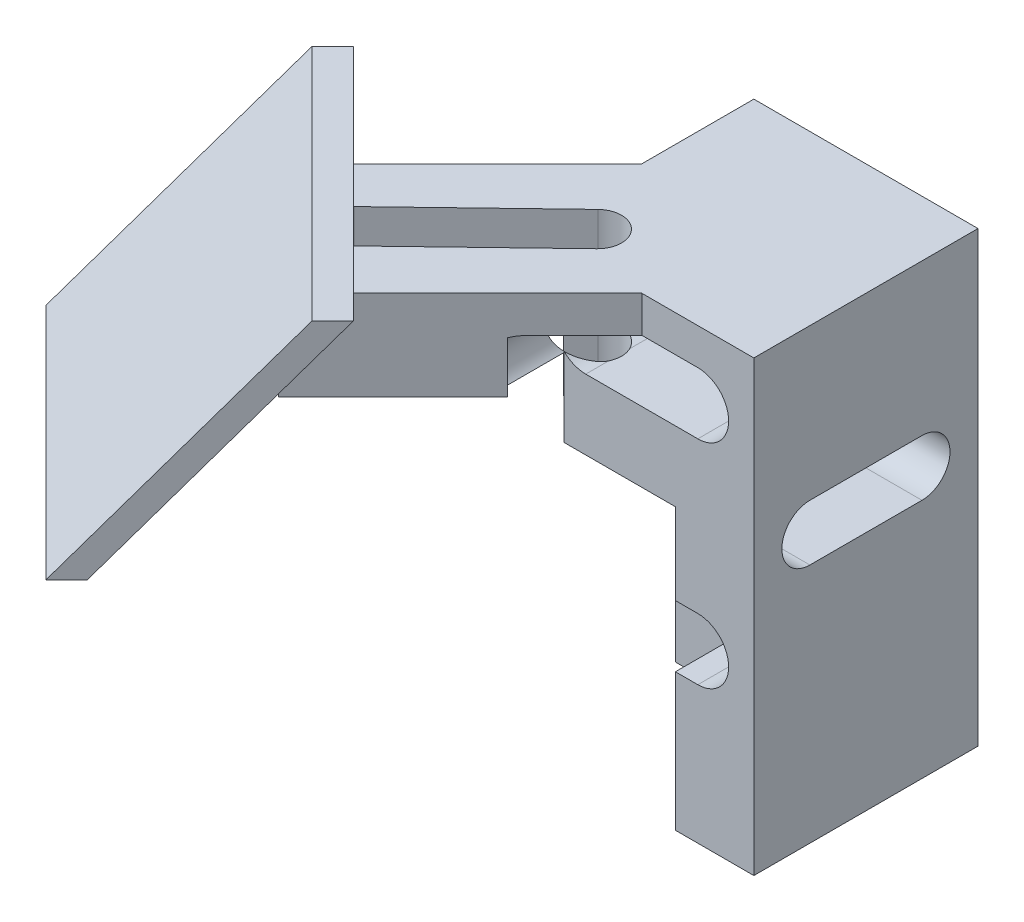
SolidWorks part; units mm, degrees
ref_plane "前视基准面" through (0, 0, 0) normal (0, 0, 1) x (1, 0, 0)
ref_plane "上视基准面" through (0, 0, 0) normal (0, 1, 0) x (1, 0, 0)
ref_plane "右视基准面" through (0, 0, 0) normal (1, 0, 0) x (0, 0, -1)
other "Configuration Table"
sketch "草图1" plane through (0, 0, 0) normal (1, 0, 0) x (0, 0, -1)
  line L1 (-10, -25) -> (10, -25)
  line L2 (-10, -25) -> (-10, 25)
  line L3 (-10, 25) -> (10, 25)
  line L4 (10, -25) -> (10, 25)
  line L5 (-10, -25) -> (10, 25) construction
  line L6 (-10, 25) -> (10, -25) construction
  point P0 (0, 0)
  dimension "D1" = 50
  dimension "D2" = 20
extrude "凸台-拉伸2" add sketch "草图1" along normal blind 20
sketch "草图2" plane through (20, 0, 0) normal (1, 0, 0) x (0, 0, -1)
  line L0 (10, -25) -> (10, 25) construction
  line L1 (-10, -25) -> (10, -25)
  line L2 (-10, -25) -> (-10, -15)
  line L3 (-10, -15) -> (10, -15)
  line L4 (10, -25) -> (10, -15)
  dimension "D1" = 10
extrude "切除-拉伸1" cut sketch "草图2" against normal blind 20
sketch "草图3" plane through (0, 0, -10) normal (0, 0, -1) x (-1, 0, 0)
  line L0 (-15, 19) -> (-5, 19) construction
  line L1 (-15, 21.75) -> (-5, 21.75)
  line L2 (-15, 16.25) -> (-5, 16.25)
  line L3 (0, -15) -> (0, 25) construction
  line L4 (-20, 25) -> (0, 25) construction
  arc A0 (-15, 21.75) -> (-15, 16.25) centre (-15, 19) ccw
  arc A1 (-5, 16.25) -> (-5, 21.75) centre (-5, 19) ccw
  point P2 (-10, 19)
  dimension "D1" = 5.5
  dimension "D2" = 5
  dimension "D3" = 10
  dimension "D4" = 6
extrude "切除-拉伸2" cut sketch "草图3" against normal blind 20
sketch "草图4" plane through (0, 0, 0) normal (-1, 0, 0) x (0, 0, 1)
  line L0 (-5, 9) -> (5, 9) construction
  line L1 (-5, 11.5) -> (5, 11.5)
  line L2 (-5, 6.5) -> (5, 6.5)
  line L3 (-10, -15) -> (10, -15) construction
  line L4 (10, 25) -> (10, -15) construction
  line L5 (-10, -15) -> (-10, 25) construction
  arc A0 (-5, 11.5) -> (-5, 6.5) centre (-5, 9) ccw
  arc A1 (5, 6.5) -> (5, 11.5) centre (5, 9) ccw
  point P2 (0, 9)
  dimension "D1" = 5
  dimension "D2" = 24
  dimension "D3" = 5
  dimension "D4" = 5
extrude "切除-拉伸3" cut sketch "草图4" against normal blind 20
sketch "草图5" plane through (0, 0, -10) normal (0, 0, -1) x (-1, 0, 0)
  line L0 (-15, 0) -> (-5, 0) construction
  line L1 (-15, 2.75) -> (-5, 2.75)
  line L2 (-15, -2.75) -> (-5, -2.75)
  line L3 (0, -15) -> (0, 25) construction
  line L4 (-20, -15) -> (-20, 25) construction
  line L5 (0, -15) -> (-20, -15) construction
  arc A0 (-15, 2.75) -> (-15, -2.75) centre (-15, 0) ccw
  arc A1 (-5, -2.75) -> (-5, 2.75) centre (-5, 0) ccw
  point P2 (-10, 0)
  dimension "D1" = 5
  dimension "D2" = 5
  dimension "D3" = 15
  dimension "D4" = 5.5
extrude "切除-拉伸4" cut sketch "草图5" against normal blind 20
sketch "草图6" plane through (0, -15, 0) normal (0, -1, 0) x (1, 0, 0)
  line L1 (0, 10) -> (13, 10)
  line L2 (0, 10) -> (0, -3)
  line L3 (0, -3) -> (13, -3)
  line L4 (13, 10) -> (13, -3)
  dimension "D1" = 13
  dimension "D2" = 13
extrude "切除-拉伸5" cut sketch "草图6" against normal blind 25
sketch "草图7" plane through (0, 25, 0) normal (0, 1, 0) x (1, 0, 0)
  line L2 (-16.2132, -16.2132) -> (-6.2132, -26.2132)
  line L3 (10, -10) -> (-6.2132, -26.2132)
  line L4 (20, -10) -> (0, -10) construction
  line L5 (0, 0) -> (-16.2132, -16.2132)
  line L6 (0, 10) -> (0, -10) construction
  line L9 (0, 0) -> (10, -10)
extrude "凸台-拉伸3" add sketch "草图7" against normal blind 8
sketch "草图8" plane through (0, 0, 0) normal (-0.7071, 0, -0.7071) x (-0.7071, 0, 0.7071)
  line L0 (18.1973, 27) -> (34.9793, 7)
  line L1 (0, 17) -> (22.9289, 17) construction
  line L3 (18.1973, 27) -> (20.8081, 27)
  line L4 (0, 25) -> (22.9289, 25) construction
  line L5 (20.8081, 27) -> (37.5901, 7)
  line L6 (13.5331, 32.5586) -> (41.8315, -1.1662) construction
  line L7 (15.0652, 33.8441) -> (43.3636, 0.1194) construction
  line L8 (34.9793, 7) -> (37.5901, 7)
  dimension "D1" = 130
  dimension "D3" = 2
  dimension "D5" = 10
  dimension "D4" = 2
extrude "凸台-拉伸6" add sketch "草图8" along normal blind 10 and the other way blind 20
sketch "草图11" plane through (10, 0, 10) normal (0.7071, 0, 0.7071) x (0.7071, 0, -0.7071)
  line L3 (-22.9289, 24.4725) -> (-22.4863, 25)
  line L4 (-22.4863, 25) -> (-22.9289, 25)
  line L5 (-22.9289, 25) -> (-22.9289, 24.4725)
  line L6 (-22.9289, 24.4725) -> (-22.4863, 25)
  line L7 (-22.4863, 25) -> (-22.9289, 25)
  line L8 (-22.9289, 25) -> (-22.9289, 24.4725)
  dimension "D1" = 0
extrude "切除-拉伸7" cut sketch "草图11" against normal blind 18
sketch "草图12" plane through (0, 0, -10) normal (0, 0, -1) x (-1, 0, 0)
  line L0 (-15, 16.25) -> (-5, 16.25) construction
  line L1 (-5, 21.75) -> (-15, 21.75) construction
  line L2 (-15, 16.25) -> (-5, 16.25)
  line L3 (-5, 21.75) -> (-15, 21.75)
  arc A0 (-5, 16.25) -> (-5, 21.75) centre (-5, 19) ccw construction
  arc A1 (-15, 21.75) -> (-15, 16.25) centre (-15, 19) ccw construction
  arc A2 (-5, 16.25) -> (-5, 21.75) centre (-5, 19) ccw
  arc A3 (-15, 21.75) -> (-15, 16.25) centre (-15, 19) ccw
extrude "切除-拉伸8" cut sketch "草图12" against normal blind 26
sketch "草图13" plane through (0, 25, 0) normal (0, 1, 0) x (1, 0, 0)
  line L0 (-8.0443, -17.6906) -> (3.063, -7.0237) construction
  line L1 (1.2747, -27.0096) -> (-19.9385, -5.7964) construction
  line L2 (-9.5345, -16.1388) -> (1.5728, -5.472)
  line L3 (-6.5541, -19.2423) -> (4.5532, -8.5755)
  arc A0 (-9.5345, -16.1388) -> (-6.5541, -19.2423) centre (-8.0443, -17.6906) ccw
  arc A1 (4.5532, -8.5755) -> (1.5728, -5.472) centre (3.063, -7.0237) ccw
  point P4 (-2.4907, -12.3571)
extrude "切除-拉伸9" cut sketch "草图13" against normal blind 26
